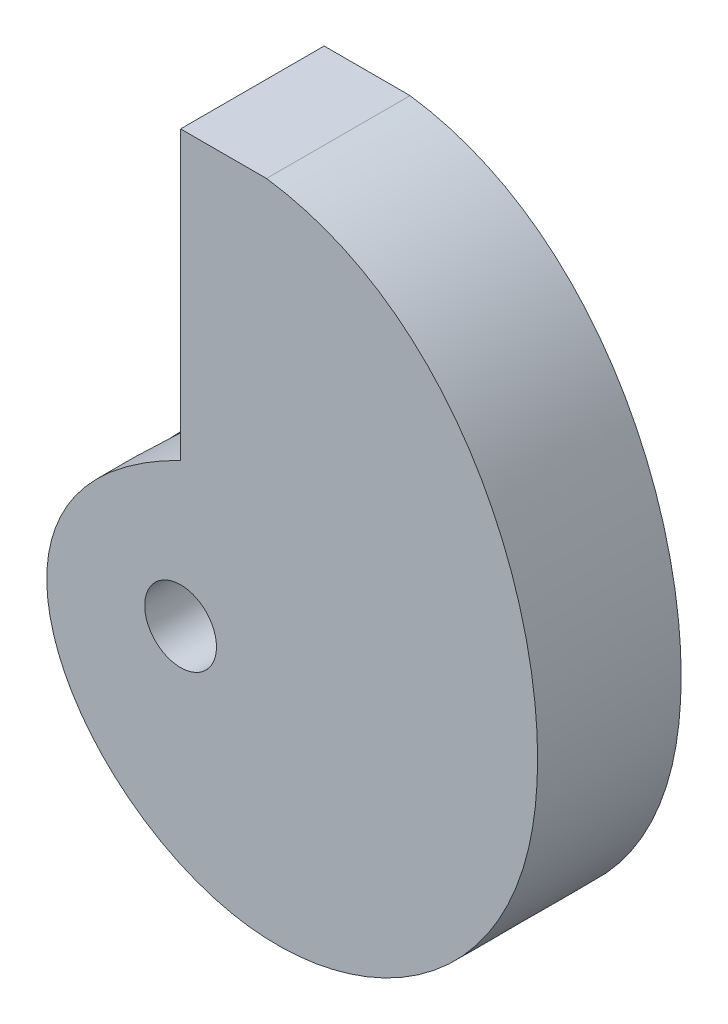
SolidWorks part; units mm, degrees
material "ABS"
ref_plane "Front Plane" through (0, 0, 0) normal (0, 0, 1) x (1, 0, 0)
ref_plane "Top Plane" through (0, 0, 0) normal (0, 1, 0) x (1, 0, 0)
ref_plane "Right Plane" through (0, 0, 0) normal (1, 0, 0) x (0, 0, -1)
sketch "Sketch1" plane through (0, 0, 0) normal (0, 0, 1) x (1, 0, 0)
  line L0 (0, 0) -> (0, 38.1)
  line L1 (-38.1, 38.1) -> (38.1, 38.1)
  line L2 (-38.1, 38.1) -> (-38.1, -38.1)
  line L3 (-38.1, -38.1) -> (38.1, -38.1)
  line L4 (38.1, 38.1) -> (38.1, -38.1)
  line L5 (-38.1, 38.1) -> (38.1, -38.1) construction
  line L6 (-38.1, -38.1) -> (38.1, 38.1) construction
  circle A0 centre (0, 0) radius 3.175
  spline S0 degree 3 poles (0, 38.1) (24.1321, 41.1545) (42.8064, -5.7788) (-0.4683, -31.5474) (-21.773, 1.9493) (0, 12.7) knots 0 0 0 0 0.338031 0.620421 1 1 1 1
  point P0 (0, 0)
  point P9 (31.1578, -0.7333)
  point P11 (1.5077, -18.1953)
  point P13 (5.0736, -19.843)
  point P16 (31.5478, 3.9683)
  point P17 (-10.8359, 1.4607)
  point P18 (-11.7199, -0.5883)
  dimension "D4" = 6.35
  dimension "D1" = 76.2
  dimension "D2" = 76.2
  dimension "D3" = 25.4
extrude "Boss-Extrude1" add sketch "Sketch1" along normal blind 12.7 contours S0 L0 A0 L4 region at (11.3082, 6.893, 0)
